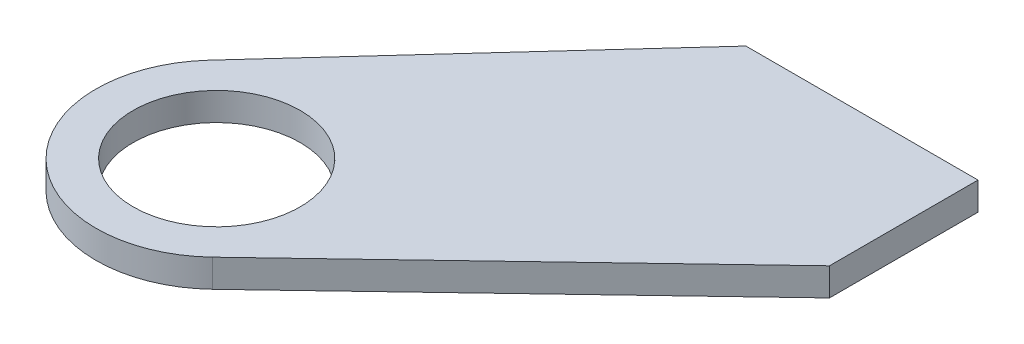
SolidWorks part; units mm, degrees
ref_plane "Front Plane" through (0, 0, 0) normal (0, 0, 1) x (1, 0, 0)
ref_plane "Top Plane" through (0, 0, 0) normal (0, 1, 0) x (1, 0, 0)
ref_plane "Right Plane" through (0, 0, 0) normal (1, 0, 0) x (0, 0, -1)
sketch "Sketch2" plane through (0, 0, 0) normal (0, 1, 0) x (1, 0, 0)
  line L0 (19.05, 0) -> (19.05, -25.4)
  line L2 (19.05, -25.4) -> (-34.9786, -76.8639)
  line L3 (19.05, 0) -> (-20.6375, 0)
  line L4 (-20.6375, 0) -> (-64.4554, -48.008)
  circle A1 centre (-49.2125, -61.9206) radius 14.2875
  arc A2 (-64.4554, -48.008) -> (-34.9786, -76.8639) centre (-49.2125, -61.9206) ccw
extrude "Boss-Extrude1" add sketch "Sketch2" along normal blind 4.7625
